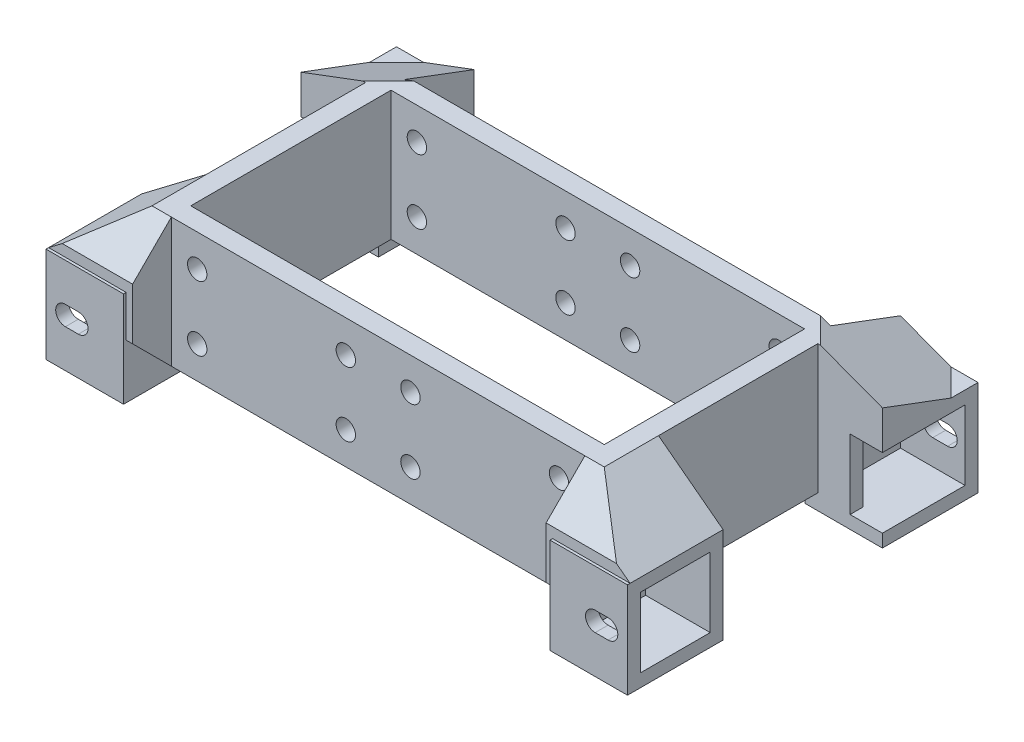
SolidWorks part; units mm, degrees
ref_plane "Front Plane" through (0, 0, 0) normal (0, 0, 1) x (1, 0, 0)
ref_plane "Top Plane" through (0, 0, 0) normal (0, 1, 0) x (1, 0, 0)
ref_plane "Right Plane" through (0, 0, 0) normal (1, 0, 0) x (0, 0, -1)
sketch "Sketch1" plane through (0, 0, 0) normal (0, 0, 1) x (1, 0, 0)
  line L1 (12.5, 10) -> (-12.5, 10)
  line L2 (12.5, 10) -> (12.5, -10)
  line L3 (12.5, -10) -> (-12.5, -10)
  line L4 (-12.5, 10) -> (-12.5, -10)
  line L5 (12.5, 10) -> (-12.5, -10) construction
  line L6 (12.5, -10) -> (-12.5, 10) construction
  point P0 (0, 0)
extrude "Boss-Extrude1" add sketch "Sketch1" along normal blind 3
sketch "Sketch2" plane through (0, 0, 3) normal (0, 0, 1) x (1, 0, 0)
  line L0 (-12.5, 10) -> (-9.5, 10)
  line L1 (12.5, 10) -> (-12.5, 10) construction
  line L2 (-9.5, 10) -> (-9.5, -10)
  line L3 (-12.5, -10) -> (12.5, -10) construction
  line L4 (-9.5, -10) -> (-12.5, -10)
  line L5 (-12.5, -10) -> (-12.5, 10)
  dimension "D1" = 3
extrude "Boss-Extrude2" add sketch "Sketch2" along normal blind 40
sketch "Sketch4" plane through (0, 0, 0) normal (0, 0, -1) x (-1, 0, 0)
  line L0 (12.5, 0) -> (-6.5, 0) construction
  line L1 (12.5, 10) -> (12.5, -10) construction
  circle A0 centre (-6.5, 0) radius 2.2
  dimension "D1" = 19
sketch "Sketch6" plane through (0, 0, 0) normal (0, 0, -1) x (-1, 0, 0)
  line L0 (-12.5, 10) -> (-57.5, 10)
  line L1 (-12.5, 10) -> (-12.5, -10)
  line L2 (-12.5, -10) -> (-57.5, -10)
  line L3 (-57.5, -10) -> (-57.5, 10)
extrude "Boss-Extrude3" add sketch "Sketch6" against normal blind 3
sketch "Sketch7" plane through (0, 0, 0) normal (0, 0, -1) x (-1, 0, 0)
  line L0 (-57.5, 0) -> (-38.5, 0) construction
  line L1 (-57.5, 10) -> (-57.5, -10) construction
  circle A0 centre (-38.5, 0) radius 2.2
  dimension "D1" = 19
sketch "Sketch9" plane through (0, 0, 3) normal (0, 0, 1) x (1, 0, 0)
  line L0 (57.5, 10) -> (54.5, 10)
  line L1 (57.5, 10) -> (-9.5, 10) construction
  line L2 (54.5, 10) -> (54.5, -10)
  line L3 (-9.5, -10) -> (57.5, -10) construction
  line L4 (54.5, -10) -> (57.5, -10)
  line L5 (57.5, -10) -> (57.5, 10)
  dimension "D1" = 3
extrude "Boss-Extrude4" add sketch "Sketch9" along normal up to surface (40 mm away) up to face at (-11, 0, 43)
sketch "Sketch3" plane through (-12.5, 0, 0) normal (-1, 0, 0) x (0, 0, 1)
  line L0 (0, 0) -> (19, 0) construction
  line L2 (0, 10) -> (0, -10) construction
  circle A0 centre (19, 0) radius 4.55
  dimension "D1" = 19
chamfer "Chamfer1" distance 6 angle 45 4 edges at (-11, -10, 43) (-11, 10, 43) (56, -10, 43) (56, 10, 43)
sketch "Sketch13" plane through (0, 0, 0) normal (0, 0, -1) x (-1, 0, 0)
  line L0 (-57.5, 10) -> (-57.5, -10)
  line L1 (-57.5, -10) -> (-55.5, -10)
  line L2 (12.5, -10) -> (-57.5, -10) construction
  line L3 (-55.5, -10) -> (-55.5, 10)
  line L4 (-57.5, 10) -> (12.5, 10) construction
  line L5 (-55.5, 10) -> (-57.5, 10)
  line L6 (12.5, 10) -> (12.5, -10)
  line L7 (12.5, -10) -> (10.5, -10)
  line L8 (12.5, -10) -> (-57.5, -10) construction
  line L9 (10.5, -10) -> (10.5, 10)
  line L10 (-57.5, 10) -> (12.5, 10) construction
  line L11 (10.5, 10) -> (12.5, 10)
  dimension "D1" = 2
  dimension "D2" = 2
sketch "Sketch17" plane through (57.5, 0, 0) normal (1, 0, 0) x (0, 0, -1)
  line L0 (8.8454, -10.4) -> (8.8454, 0.4)
  line L1 (8.4454, -10) -> (-1.5546, -10) construction
  line L2 (8.4454, -10) -> (8.4454, 0) construction
  line L3 (8.4454, 0) -> (-1.5546, 0) construction
  line L4 (-1.5546, -10) -> (-1.5546, 0) construction
  line L5 (8.8454, 0.4) -> (-1.9546, 0.4)
  line L6 (-1.9546, -10.4) -> (-1.9546, 0.4)
  line L7 (8.8454, -10.4) -> (-1.9546, -10.4)
  line L8 (10.8454, -12.4) -> (10.8454, 2.4)
  line L9 (10.8454, 2.4) -> (-3.9546, 2.4)
  line L10 (-3.9546, -12.4) -> (-3.9546, 2.4)
  line L11 (10.8454, -12.4) -> (-3.9546, -12.4)
  line L12 (-1.9546, 0.4) -> (8.8454, -10.4) construction
  line L13 (8.8454, 0.4) -> (-1.9546, -10.4) construction
  line L14 (3.4454, -5) -> (-36.0046, -5) construction
  line L15 (-30.6046, -10.4) -> (-30.6046, 0.4)
  line L16 (-31.0046, -10) -> (-41.0046, -10) construction
  line L17 (-31.0046, -10) -> (-31.0046, 0) construction
  line L18 (-31.0046, 0) -> (-41.0046, 0) construction
  line L19 (-41.0046, -10) -> (-41.0046, 0) construction
  line L20 (-30.6046, 0.4) -> (-41.4046, 0.4)
  line L21 (-41.4046, -10.4) -> (-41.4046, 0.4)
  line L22 (-30.6046, -10.4) -> (-41.4046, -10.4)
  line L23 (-28.6046, -12.4) -> (-28.6046, 2.4)
  line L24 (-28.6046, 2.4) -> (-43.4046, 2.4)
  line L25 (-43.4046, -12.4) -> (-43.4046, 2.4)
  line L26 (-28.6046, -12.4) -> (-43.4046, -12.4)
  line L27 (-41.4046, 0.4) -> (-30.6046, -10.4) construction
  line L28 (-30.6046, 0.4) -> (-41.4046, -10.4) construction
  dimension "D3" = 39.45
  dimension "D4" = 14.8
  dimension "D1" = 0.4
  dimension "D2" = 2
extrude "Boss-Extrude7" add sketch "Sketch17" along normal blind 10
ref_point "Point1"
ref_point "Point2"
ref_axis "Axis1" through (22.5, 0, 0) along (0, 0, 1)
ref_plane "Plane1" through (22.5, 0, 0) normal (-1, 0, 0) x (0, 0, 1)
sketch "Sketch18" plane through (57.5, 0, 0) normal (-1, 0, 0) x (0, 0, 1)
  line L1 (-10.8454, 2.4) -> (3.9546, 2.4)
  line L2 (-10.8454, 2.4) -> (-10.8454, -12.4)
  line L3 (-10.8454, -12.4) -> (3.9546, -12.4)
  line L4 (3.9546, 2.4) -> (3.9546, -12.4)
extrude "Boss-Extrude8" add sketch "Sketch18" along normal blind 2
sketch "Sketch21" plane through (57.5, 0, 0) normal (-1, 0, 0) x (0, 0, 1)
  line L1 (28.6046, 2.4) -> (43.4046, 2.4)
  line L2 (28.6046, 2.4) -> (28.6046, -12.4)
  line L3 (28.6046, -12.4) -> (43.4046, -12.4)
  line L4 (43.4046, 2.4) -> (43.4046, -12.4)
extrude "Boss-Extrude11" add sketch "Sketch21" along normal blind 2
sketch "Sketch22" plane through (0, 0, 43.4046) normal (0, 0, 1) x (1, 0, 0)
  line L0 (57.5, 2.4) -> (57.5, 10)
  line L1 (57.5, 10) -> (67.5, 2.4)
  line L2 (67.5, 2.4) -> (57.5, 2.4)
extrude "Boss-Extrude12" add sketch "Sketch22" against normal up to surface (14.8 mm away) up to face at (60.1667, -6.6667, 28.6046)
sketch "Sketch23" plane through (0, 2.4, 0) normal (0, 1, 0) x (1, 0, 0)
  line L0 (55.5, 0) -> (57.5, 0)
  line L1 (57.5, 0) -> (57.5, -3.9546)
  line L2 (67.5, -3.9546) -> (57.5, -3.9546) construction
  line L3 (57.5, -28.6046) -> (57.5, 0) construction
  line L4 (57.5, -3.9546) -> (67.5, -3.9546)
  line L5 (67.5, -3.9546) -> (67.5, 10.4929)
  line L6 (67.5, 10.8454) -> (67.5, -3.9546) construction
  line L7 (67.5, 10.4929) -> (67.1475, 10.8454)
  line L8 (67.5, 10.8454) -> (55.5, 10.8454) construction
  line L9 (67.1475, 10.8454) -> (55.5, 10.8454)
  line L10 (55.5, 10.8454) -> (55.5, 0)
extrude "Boss-Extrude13" add sketch "Sketch23" along normal up to surface (7.6 mm away) up to face at (29.9444, 10, 22.1783)
chamfer "Chamfer4" distance 17 angle 28 1 edges at (67.3237, 10, -10.6691) first distance on face at (41.6177, 10, 12.5236)
sketch "Sketch24" plane through (57.5, 0, 0) normal (-1, 0, 0) x (0, 0, 1)
  line L0 (37, 10) -> (43.4046, 10)
  line L1 (43.4046, 10) -> (43.4046, 2.4)
  line L2 (43.4046, 2.4) -> (43, 2.4)
  line L3 (43, 2.4) -> (43, 4)
  line L4 (43, 4) -> (37, 10)
extrude "Cut-Extrude8" cut sketch "Sketch24" against normal blind 13
mirror "Mirror3" about plane through (22.5, 0, 0) normal (-1, 0, 0) of "Boss-Extrude8", "Boss-Extrude7", "Boss-Extrude11", "Boss-Extrude13", "Boss-Extrude12", "Chamfer4", "Cut-Extrude8"
sketch "Sketch27" plane through (-22.5, 0, 0) normal (-1, 0, 0) x (0, 0, 1)
  line L0 (3.9546, 6.3928) -> (3.9546, -12.4) construction
  line L1 (1.9546, 0.4) -> (3.9546, 0.4)
  line L2 (1.9546, 0.4) -> (1.9546, -10.4)
  line L3 (1.9546, -10.4) -> (3.9546, -10.4)
  line L4 (3.9546, 0.4) -> (3.9546, -10.4)
extrude "Cut-Extrude10" cut sketch "Sketch27" against normal blind 3
mirror "Mirror4" about plane through (22.5, 0, 0) normal (-1, 0, 0) of "Cut-Extrude10"
sketch "Sketch32" plane through (0, 0, -10.8454) normal (0, 0, -1) x (-1, 0, 0)
  line L0 (22.5, -5) -> (10.5, -5) construction
  line L1 (22.5, -12.4) -> (22.5, 2.4) construction
  line L2 (10.5, -10) -> (10.5, 10) construction
  line L3 (19.7902, -5) -> (17.5, -5) construction
  line L4 (19.7902, -6.5) -> (17.5, -6.5)
  line L5 (19.7902, -3.5) -> (17.5, -3.5)
  line L6 (-22.5, 10) -> (-22.5, -18.9025) construction
  line L7 (-53.9513, 10) -> (8.9513, 10) construction
  line L8 (-67.5, -5) -> (-55.5, -5) construction
  line L9 (-64.7902, -5) -> (-62.5, -5) construction
  line L10 (-64.7902, -6.5) -> (-62.5, -6.5)
  line L11 (-64.7902, -3.5) -> (-62.5, -3.5)
  arc A0 (19.7902, -6.5) -> (19.7902, -3.5) centre (19.7902, -5) ccw
  arc A1 (17.5, -3.5) -> (17.5, -6.5) centre (17.5, -5) ccw
  arc A2 (-64.7902, -6.5) -> (-64.7902, -3.5) centre (-64.7902, -5) cw
  arc A3 (-62.5, -3.5) -> (-62.5, -6.5) centre (-62.5, -5) cw
  point P8 (18.6451, -5)
  point P21 (-63.6451, -5)
extrude "Cut-Extrude12" cut sketch "Sketch32" against normal blind 10
sketch "Sketch33" plane through (0, 0, 43.4046) normal (0, 0, 1) x (1, 0, 0)
  line L0 (67.5, -5) -> (55.5, -5) construction
  line L1 (67.5, 2.4) -> (67.5, -12.4) construction
  line L2 (55.5, -12.4) -> (55.5, 2.4) construction
  line L3 (62.5, -5) -> (64.5, -5) construction
  line L4 (62.5, -3.5) -> (64.5, -3.5)
  line L5 (62.5, -6.5) -> (64.5, -6.5)
  line L6 (-22.5, -5) -> (-10.5, -5) construction
  line L7 (-22.5, 2.4) -> (-22.5, -12.4) construction
  line L8 (-10.5, -12.4) -> (-10.5, 2.4) construction
  line L9 (-17.5, -5) -> (-19.5, -5) construction
  line L10 (-17.5, -6.5) -> (-19.5, -6.5)
  line L11 (-17.5, -3.5) -> (-19.5, -3.5)
  arc A0 (62.5, -3.5) -> (62.5, -6.5) centre (62.5, -5) ccw
  arc A1 (64.5, -6.5) -> (64.5, -3.5) centre (64.5, -5) ccw
  arc A2 (-17.5, -6.5) -> (-17.5, -3.5) centre (-17.5, -5) ccw
  arc A3 (-19.5, -3.5) -> (-19.5, -6.5) centre (-19.5, -5) ccw
  point P8 (63.5, -5)
  point P21 (-18.5, -5)
  dimension "D1" = 3
  dimension "D2" = 2
  dimension "D3" = 3
  dimension "D4" = 4
  dimension "D5" = 4
extrude "Cut-Extrude13" cut sketch "Sketch33" against normal blind 10
sketch "Sketch40" plane through (64.5, 0, 0) normal (1, 0, 0) x (0, 0, -1)
  line L0 (-3.9546, 0.4) -> (-1.9546, 0.4)
  line L1 (-1.9546, 0.4) -> (-1.9546, -10.4)
  line L2 (-1.9546, -10.4) -> (-3.9546, -10.4)
  line L3 (-3.9546, -10.4) -> (-3.9546, 0.4)
extrude "Cut-Extrude16" cut sketch "Sketch40" against normal blind 2
sketch "Sketch41" plane through (-19.5, 0, 0) normal (-1, 0, 0) x (0, 0, 1)
  line L0 (1.9546, 0.4) -> (3.9546, 0.4)
  line L1 (3.9546, 0.4) -> (3.9546, -10.4)
  line L2 (3.9546, -10.4) -> (1.9546, -10.4)
  line L3 (1.9546, -10.4) -> (1.9546, 0.4)
extrude "Cut-Extrude17" cut sketch "Sketch41" against normal blind 2
sketch "Sketch51" plane through (-9.5, 0, 0) normal (1, 0, 0) x (0, 0, -1)
  line L0 (-37, 10) -> (-37, -10)
  line L1 (-37, -10) -> (-34, -10)
  line L2 (-37, -10) -> (-28.6046, -10) construction
  line L3 (-34, -10) -> (-34, 10)
  line L4 (-37, 10) -> (-3, 10) construction
  line L5 (-34, 10) -> (-37, 10)
extrude "Boss-Extrude14" add sketch "Sketch51" along normal up to surface (64 mm away) up to face at (54.5, 0, 27.6667)
sketch "Sketch50" plane through (0, 0, 0) normal (0, 0, -1) x (-1, 0, 0)
  line L0 (-22.5, 10) -> (-22.5, -10) construction
  line L1 (-53.9513, 10) -> (8.9513, 10) construction
  line L2 (10.5, -10) -> (-55.5, -10) construction
  line L3 (-22.5, 0) -> (-55.5, 0) construction
  line L5 (-55.5, 5.3401) -> (-55.5, -12.4) construction
  line L6 (-22.5, 0) -> (10.5, 0) construction
  line L7 (10.5, 9.4177) -> (10.5, -10) construction
  line L8 (5.5, 0) -> (5.5, 5) construction
  line L9 (5.5, 0) -> (5.5, -5) construction
  line L10 (-27.5, 0) -> (-27.5, 5) construction
  circle A0 centre (5.5, 5) radius 1.5
  circle A1 centre (5.5, -5) radius 1.5
  circle A2 centre (-50.5, -5) radius 1.5
  circle A3 centre (-50.5, 5) radius 1.5
  circle A4 centre (-27.5, 5) radius 1.5
  circle A5 centre (-27.5, -5) radius 1.5
  circle A6 centre (-17.5, -5) radius 1.5
  circle A7 centre (-17.5, 5) radius 1.5
  dimension "D1" = 28
  dimension "D2" = 5
extrude "Cut-Extrude22" cut sketch "Sketch50" against normal through all
